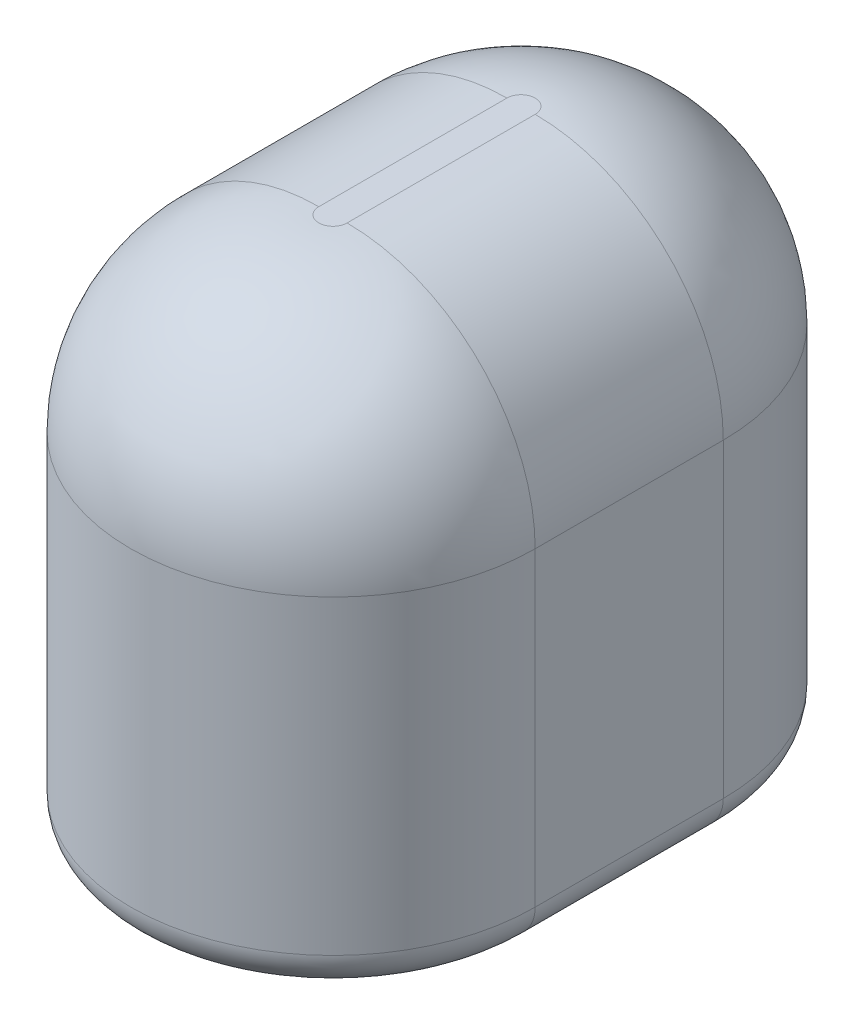
SolidWorks part; units mm, degrees
material "Glass"
ref_plane "Front Plane" through (0, 0, 0) normal (0, 0, 1) x (1, 0, 0)
ref_plane "Top Plane" through (0, 0, 0) normal (0, 1, 0) x (1, 0, 0)
ref_plane "Right Plane" through (0, 0, 0) normal (1, 0, 0) x (0, 0, -1)
sketch "Sketch1" plane through (0, 0, 0) normal (0, 1, 0) x (1, 0, 0)
  line L0 (0, -5) -> (0, 5) construction
  line L1 (-10.75, -5) -> (-10.75, 5)
  line L2 (10.75, -5) -> (10.75, 5)
  arc A0 (-10.75, -5) -> (10.75, -5) centre (0, -5) ccw
  arc A1 (10.75, 5) -> (-10.75, 5) centre (0, 5) ccw
  point P2 (0, 0)
  point P8 (0, 15.75)
  point P9 (0, -15.75)
  dimension "D1" = 21.5
  dimension "D2" = 31.5
extrude "Boss-Extrude1" add sketch "Sketch1" along normal blind 28.5
fillet "Fillet2" radius 10 4 edges at (-10.75, 28.5, 0) (0, 28.5, -15.75) (10.75, 28.5, 0) (0, 28.5, 15.75)
fillet "Fillet3" radius 2 4 edges at (-10.75, 0, 0) (0, 0, -15.75) (10.75, 0, 0) (0, 0, 15.75)
sketch "Sketch2" plane through (0, 0, 0) normal (0, -1, 0) x (1, 0, 0)
  circle A0 centre (0, 0) radius 1.75
  dimension "D1" = 3.5
extrude "Boss-Extrude2" add sketch "Sketch2" along normal blind 7
fillet "Fillet4" radius 1 1 edges at (0, -7, -1.75)
fillet "Fillet5" radius 0.5 1 edges at (0, 0, 1.75)
shell "Shell2" thickness 1
